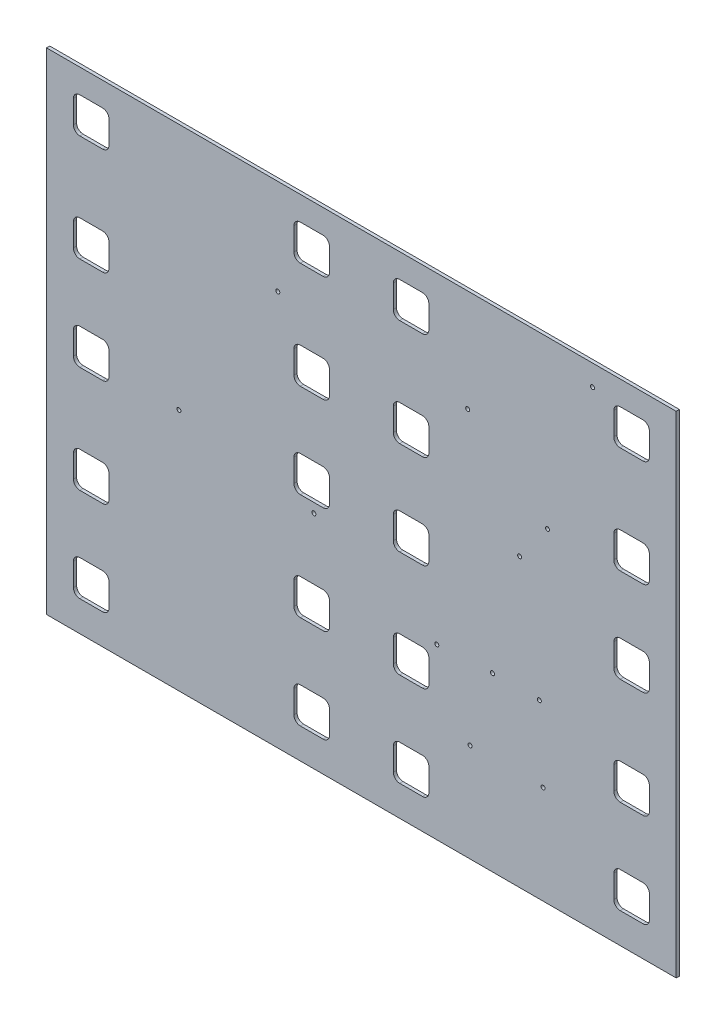
SolidWorks part; units mm, degrees
material "ABS"
ref_plane "X-Y Datum" through (0, 0, 0) normal (0, 0, 1) x (1, 0, 0)
ref_plane "X-Z Datum" through (0, 0, 0) normal (0, 1, 0) x (1, 0, 0)
ref_plane "Y-Z Datum" through (0, 0, 0) normal (1, 0, 0) x (0, 0, -1)
sketch "Sketch9" plane through (0, 0, 0) normal (0, 0, 1) x (1, 0, 0)
  line L0 (-82.7559, -182.5893) -> (-82.7583, -160.1613) construction
  line L1 (-89.109, -153.8119) -> (-111.537, -153.8143) construction
  line L2 (-117.8863, -160.165) -> (-117.8839, -182.593) construction
  line L3 (-111.5333, -188.9423) -> (-89.1053, -188.9399) construction
  line L4 (476.934, -311.4483) -> (476.8831, 172.8027)
  line L5 (476.8831, 172.8027) -> (-144.3755, 172.7375)
  line L6 (-144.3755, 172.7375) -> (-144.3246, -311.5135)
  line L7 (-144.3246, -311.5135) -> (476.934, -311.4483)
  line L8 (476.934, -311.4483) -> (476.8831, 172.8027)
  line L9 (476.8831, 172.8027) -> (-144.3755, 172.7375)
  line L10 (-144.3755, 172.7375) -> (-144.3246, -311.5135)
  line L11 (-144.3246, -311.5135) -> (476.934, -311.4483)
  line L12 (-111.5443, -83.8117) -> (-89.1163, -83.8093) construction
  line L13 (-82.767, -77.4587) -> (-82.7693, -55.0307) construction
  line L14 (-89.12, -48.6813) -> (-111.548, -48.6837) construction
  line L15 (-117.8973, -55.0344) -> (-117.895, -77.4624) construction
  line L16 (-82.7877, 120.2549) -> (-82.7901, 142.6829) construction
  line L17 (-89.1408, 149.0323) -> (-111.5688, 149.0299) construction
  line L18 (-117.9181, 142.6792) -> (-117.9157, 120.2512) construction
  line L19 (-111.5651, 113.9019) -> (-89.1371, 113.9043) construction
  line L20 (-111.554, 8.7713) -> (-89.126, 8.7737) construction
  line L21 (-117.9071, 37.5486) -> (-117.9047, 15.1206) construction
  line L22 (-89.1297, 43.9017) -> (-111.5577, 43.8993) construction
  line L23 (-82.7767, 15.1243) -> (-82.7791, 37.5523) construction
  line L24 (-82.7559, -182.5893) -> (-82.7583, -160.1613)
  line L25 (-89.109, -153.8119) -> (-111.537, -153.8143)
  line L26 (-117.8863, -160.165) -> (-117.8839, -182.593)
  line L27 (-111.5333, -188.9423) -> (-89.1053, -188.9399)
  line L28 (-111.5443, -83.8117) -> (-89.1163, -83.8093)
  line L29 (-82.767, -77.4587) -> (-82.7693, -55.0307)
  line L30 (-89.12, -48.6813) -> (-111.548, -48.6837)
  line L31 (-117.8973, -55.0344) -> (-117.895, -77.4624)
  line L32 (-82.7877, 120.2549) -> (-82.7901, 142.6829)
  line L33 (-89.1408, 149.0323) -> (-111.5688, 149.0299)
  line L34 (-117.9181, 142.6792) -> (-117.9157, 120.2512)
  line L35 (-111.5651, 113.9019) -> (-89.1371, 113.9043)
  line L36 (-111.554, 8.7713) -> (-89.126, 8.7737)
  line L37 (-117.9071, 37.5486) -> (-117.9047, 15.1206)
  line L38 (-89.1297, 43.9017) -> (-111.5577, 43.8993)
  line L39 (-82.7767, 15.1243) -> (-82.7791, 37.5523)
  line L40 (-82.7462, -275.1723) -> (-82.7486, -252.7443) construction
  line L41 (-89.0992, -246.3949) -> (-111.5272, -246.3973) construction
  line L42 (-117.8766, -252.748) -> (-117.8742, -275.176) construction
  line L43 (-111.5235, -281.5253) -> (-89.0955, -281.5229) construction
  line L44 (-82.7462, -275.1723) -> (-82.7486, -252.7443)
  line L45 (-89.0992, -246.3949) -> (-111.5272, -246.3973)
  line L46 (-117.8766, -252.748) -> (-117.8742, -275.176)
  line L47 (-111.5235, -281.5253) -> (-89.0955, -281.5229)
  arc A0 (-89.1053, -188.9399) -> (-82.7559, -182.5893) centre (-89.1059, -182.5899) ccw construction
  arc A1 (-82.7583, -160.1613) -> (-89.109, -153.8119) centre (-89.1083, -160.1619) ccw construction
  arc A2 (-111.537, -153.8143) -> (-117.8863, -160.165) centre (-111.5363, -160.1643) ccw construction
  arc A3 (-117.8839, -182.593) -> (-111.5333, -188.9423) centre (-111.5339, -182.5923) ccw construction
  arc A4 (-89.1163, -83.8093) -> (-82.767, -77.4587) centre (-89.117, -77.4593) ccw construction
  arc A5 (-82.7693, -55.0307) -> (-89.12, -48.6813) centre (-89.1193, -55.0313) ccw construction
  arc A6 (-111.548, -48.6837) -> (-117.8973, -55.0344) centre (-111.5473, -55.0337) ccw construction
  arc A7 (-117.895, -77.4624) -> (-111.5443, -83.8117) centre (-111.545, -77.4617) ccw construction
  arc A8 (-89.1371, 113.9043) -> (-82.7877, 120.2549) centre (-89.1377, 120.2543) ccw construction
  arc A9 (-82.7901, 142.6829) -> (-89.1408, 149.0323) centre (-89.1401, 142.6823) ccw construction
  arc A10 (-111.5688, 149.0299) -> (-117.9181, 142.6792) centre (-111.5681, 142.6799) ccw construction
  arc A11 (-117.9157, 120.2512) -> (-111.5651, 113.9019) centre (-111.5657, 120.2519) ccw construction
  arc A12 (-82.7791, 37.5523) -> (-89.1297, 43.9017) centre (-89.1291, 37.5517) ccw construction
  arc A13 (-89.126, 8.7737) -> (-82.7767, 15.1243) centre (-89.1267, 15.1237) ccw construction
  arc A14 (-117.9047, 15.1206) -> (-111.554, 8.7713) centre (-111.5547, 15.1213) ccw construction
  arc A15 (-111.5577, 43.8993) -> (-117.9071, 37.5486) centre (-111.5571, 37.5493) ccw construction
  arc A16 (-89.1053, -188.9399) -> (-82.7559, -182.5893) centre (-89.1059, -182.5899) ccw
  arc A17 (-82.7583, -160.1613) -> (-89.109, -153.8119) centre (-89.1083, -160.1619) ccw
  arc A18 (-111.537, -153.8143) -> (-117.8863, -160.165) centre (-111.5363, -160.1643) ccw
  arc A19 (-117.8839, -182.593) -> (-111.5333, -188.9423) centre (-111.5339, -182.5923) ccw
  arc A20 (-89.1163, -83.8093) -> (-82.767, -77.4587) centre (-89.117, -77.4593) ccw
  arc A21 (-82.7693, -55.0307) -> (-89.12, -48.6813) centre (-89.1193, -55.0313) ccw
  arc A22 (-111.548, -48.6837) -> (-117.8973, -55.0344) centre (-111.5473, -55.0337) ccw
  arc A23 (-117.895, -77.4624) -> (-111.5443, -83.8117) centre (-111.545, -77.4617) ccw
  arc A24 (-89.1371, 113.9043) -> (-82.7877, 120.2549) centre (-89.1377, 120.2543) ccw
  arc A25 (-82.7901, 142.6829) -> (-89.1408, 149.0323) centre (-89.1401, 142.6823) ccw
  arc A26 (-111.5688, 149.0299) -> (-117.9181, 142.6792) centre (-111.5681, 142.6799) ccw
  arc A27 (-117.9157, 120.2512) -> (-111.5651, 113.9019) centre (-111.5657, 120.2519) ccw
  arc A28 (-82.7791, 37.5523) -> (-89.1297, 43.9017) centre (-89.1291, 37.5517) ccw
  arc A29 (-89.126, 8.7737) -> (-82.7767, 15.1243) centre (-89.1267, 15.1237) ccw
  arc A30 (-117.9047, 15.1206) -> (-111.554, 8.7713) centre (-111.5547, 15.1213) ccw
  arc A31 (-111.5577, 43.8993) -> (-117.9071, 37.5486) centre (-111.5571, 37.5493) ccw
  arc A32 (-89.0955, -281.5229) -> (-82.7462, -275.1723) centre (-89.0962, -275.1729) ccw construction
  arc A33 (-111.5272, -246.3973) -> (-117.8766, -252.748) centre (-111.5266, -252.7473) ccw construction
  arc A34 (-117.8742, -275.176) -> (-111.5235, -281.5253) centre (-111.5242, -275.1753) ccw construction
  arc A35 (-89.0955, -281.5229) -> (-82.7462, -275.1723) centre (-89.0962, -275.1729) ccw
  arc A36 (-111.5272, -246.3973) -> (-117.8766, -252.748) centre (-111.5266, -252.7473) ccw
  arc A37 (-117.8742, -275.176) -> (-111.5235, -281.5253) centre (-111.5242, -275.1753) ccw
  arc A38 (-82.7486, -252.7443) -> (-89.0992, -246.3949) centre (-89.0986, -252.7449) ccw construction
  arc A39 (-82.7486, -252.7443) -> (-89.0992, -246.3949) centre (-89.0986, -252.7449) ccw
  dimension "D1" = 0
extrude "Boss-Extrude2" add sketch "Sketch9" along normal blind 3.175 contours L10 L11 L8 L9 A39 L44 A35 L47 A37 L46 A36 L45 A31 L38 A28 L39 A29 L36 A30 L37 A27 L34 A26 L33 A25 L32 A24 L35 A23 L31 A22 L30 A21 L29 A20 L28 A19 L26 A18 L25 A17 L24 A16 L27 | L44 A39 L45 A36 L46 A37 L47 A35 | L26 A19 L27 A16 L24 A17 L25 A18 | L38 A31 L37 A30 L36 A29 L39 A28 | L34 A27 L35 A24 L32 A25 L33 A26 | L31 A23 L28 A20 L29 A21 L30 A22 region at (171.7018, -69.3676, 0) region at (-100.3211, -171.3771, 0) region at (-100.3322, -66.2465, 0) region at (-100.3529, 131.4671, 0) region at (-100.3419, 26.3365, 0) region at (-100.3114, -263.9601, 0)
sketch "Sketch10" plane through (0, 0, 3.175) normal (0, 0, 1) x (1, 0, 0)
  line L4 (476.934, -311.4483) -> (476.8831, 172.8027)
  line L5 (476.8831, 172.8027) -> (-144.3755, 172.7375)
  line L6 (-144.3755, 172.7375) -> (-144.3246, -311.5135)
  line L7 (-144.3246, -311.5135) -> (476.934, -311.4483)
  line L8 (476.934, -311.4483) -> (476.8831, 172.8027)
  line L9 (476.8831, 172.8027) -> (-144.3755, 172.7375)
  line L10 (-144.3755, 172.7375) -> (-144.3246, -311.5135)
  line L11 (-144.3246, -311.5135) -> (476.934, -311.4483)
  line L12 (-117.8863, -160.165) -> (-117.8839, -182.593)
  line L13 (-111.5333, -188.9423) -> (-89.1053, -188.9399)
  line L14 (-82.7559, -182.5893) -> (-82.7583, -160.1613)
  line L15 (-89.109, -153.8119) -> (-111.537, -153.8143)
  line L16 (-117.8863, -160.165) -> (-117.8839, -182.593)
  line L17 (-111.5333, -188.9423) -> (-89.1053, -188.9399)
  line L18 (-82.7559, -182.5893) -> (-82.7583, -160.1613)
  line L19 (-89.109, -153.8119) -> (-111.537, -153.8143)
  line L20 (-117.8766, -252.748) -> (-117.8742, -275.176)
  line L21 (-89.0992, -246.3949) -> (-111.5272, -246.3973)
  line L22 (-82.7462, -275.1723) -> (-82.7486, -252.7443)
  line L23 (-111.5235, -281.5253) -> (-89.0955, -281.5229)
  line L24 (-117.8766, -252.748) -> (-117.8742, -275.176)
  line L25 (-89.0992, -246.3949) -> (-111.5272, -246.3973)
  line L26 (-82.7462, -275.1723) -> (-82.7486, -252.7443)
  line L27 (-111.5235, -281.5253) -> (-89.0955, -281.5229)
  line L28 (-89.12, -48.6813) -> (-111.548, -48.6837)
  line L29 (-117.8973, -55.0344) -> (-117.895, -77.4624)
  line L30 (-111.5443, -83.8117) -> (-89.1163, -83.8093)
  line L31 (-82.767, -77.4587) -> (-82.7693, -55.0307)
  line L32 (-89.12, -48.6813) -> (-111.548, -48.6837)
  line L33 (-117.8973, -55.0344) -> (-117.895, -77.4624)
  line L34 (-111.5443, -83.8117) -> (-89.1163, -83.8093)
  line L35 (-82.767, -77.4587) -> (-82.7693, -55.0307)
  line L36 (-82.7877, 120.2549) -> (-82.7901, 142.6829)
  line L37 (-111.5651, 113.9019) -> (-89.1371, 113.9043)
  line L38 (-117.9181, 142.6792) -> (-117.9157, 120.2512)
  line L39 (-89.1408, 149.0323) -> (-111.5688, 149.0299)
  line L40 (-82.7877, 120.2549) -> (-82.7901, 142.6829)
  line L41 (-111.5651, 113.9019) -> (-89.1371, 113.9043)
  line L42 (-117.9181, 142.6792) -> (-117.9157, 120.2512)
  line L43 (-89.1408, 149.0323) -> (-111.5688, 149.0299)
  line L44 (-111.554, 8.7713) -> (-89.126, 8.7737)
  line L45 (-82.7767, 15.1243) -> (-82.7791, 37.5523)
  line L46 (-89.1297, 43.9017) -> (-111.5577, 43.8993)
  line L47 (-117.9071, 37.5486) -> (-117.9047, 15.1206)
  line L48 (-111.554, 8.7713) -> (-89.126, 8.7737)
  line L49 (-82.7767, 15.1243) -> (-82.7791, 37.5523)
  line L50 (-89.1297, 43.9017) -> (-111.5577, 43.8993)
  line L51 (-117.9071, 37.5486) -> (-117.9047, 15.1206)
  arc A4 (-117.8839, -182.593) -> (-111.5333, -188.9423) centre (-111.5339, -182.5923) ccw
  arc A5 (-89.1053, -188.9399) -> (-82.7559, -182.5893) centre (-89.1059, -182.5899) ccw
  arc A6 (-82.7583, -160.1613) -> (-89.109, -153.8119) centre (-89.1083, -160.1619) ccw
  arc A7 (-111.537, -153.8143) -> (-117.8863, -160.165) centre (-111.5363, -160.1643) ccw
  arc A8 (-117.8839, -182.593) -> (-111.5333, -188.9423) centre (-111.5339, -182.5923) ccw
  arc A9 (-89.1053, -188.9399) -> (-82.7559, -182.5893) centre (-89.1059, -182.5899) ccw
  arc A10 (-82.7583, -160.1613) -> (-89.109, -153.8119) centre (-89.1083, -160.1619) ccw
  arc A11 (-111.537, -153.8143) -> (-117.8863, -160.165) centre (-111.5363, -160.1643) ccw
  arc A12 (-111.5272, -246.3973) -> (-117.8766, -252.748) centre (-111.5266, -252.7473) ccw
  arc A13 (-82.7486, -252.7443) -> (-89.0992, -246.3949) centre (-89.0986, -252.7449) ccw
  arc A14 (-89.0955, -281.5229) -> (-82.7462, -275.1723) centre (-89.0962, -275.1729) ccw
  arc A15 (-117.8742, -275.176) -> (-111.5235, -281.5253) centre (-111.5242, -275.1753) ccw
  arc A16 (-111.5272, -246.3973) -> (-117.8766, -252.748) centre (-111.5266, -252.7473) ccw
  arc A17 (-82.7486, -252.7443) -> (-89.0992, -246.3949) centre (-89.0986, -252.7449) ccw
  arc A18 (-89.0955, -281.5229) -> (-82.7462, -275.1723) centre (-89.0962, -275.1729) ccw
  arc A19 (-117.8742, -275.176) -> (-111.5235, -281.5253) centre (-111.5242, -275.1753) ccw
  arc A20 (-111.548, -48.6837) -> (-117.8973, -55.0344) centre (-111.5473, -55.0337) ccw
  arc A21 (-117.895, -77.4624) -> (-111.5443, -83.8117) centre (-111.545, -77.4617) ccw
  arc A22 (-89.1163, -83.8093) -> (-82.767, -77.4587) centre (-89.117, -77.4593) ccw
  arc A23 (-82.7693, -55.0307) -> (-89.12, -48.6813) centre (-89.1193, -55.0313) ccw
  arc A24 (-111.548, -48.6837) -> (-117.8973, -55.0344) centre (-111.5473, -55.0337) ccw
  arc A25 (-117.895, -77.4624) -> (-111.5443, -83.8117) centre (-111.545, -77.4617) ccw
  arc A26 (-89.1163, -83.8093) -> (-82.767, -77.4587) centre (-89.117, -77.4593) ccw
  arc A27 (-82.7693, -55.0307) -> (-89.12, -48.6813) centre (-89.1193, -55.0313) ccw
  arc A28 (-89.1371, 113.9043) -> (-82.7877, 120.2549) centre (-89.1377, 120.2543) ccw
  arc A29 (-117.9157, 120.2512) -> (-111.5651, 113.9019) centre (-111.5657, 120.2519) ccw
  arc A30 (-111.5688, 149.0299) -> (-117.9181, 142.6792) centre (-111.5681, 142.6799) ccw
  arc A31 (-82.7901, 142.6829) -> (-89.1408, 149.0323) centre (-89.1401, 142.6823) ccw
  arc A32 (-89.1371, 113.9043) -> (-82.7877, 120.2549) centre (-89.1377, 120.2543) ccw
  arc A33 (-117.9157, 120.2512) -> (-111.5651, 113.9019) centre (-111.5657, 120.2519) ccw
  arc A34 (-111.5688, 149.0299) -> (-117.9181, 142.6792) centre (-111.5681, 142.6799) ccw
  arc A35 (-82.7901, 142.6829) -> (-89.1408, 149.0323) centre (-89.1401, 142.6823) ccw
  arc A36 (-89.126, 8.7737) -> (-82.7767, 15.1243) centre (-89.1267, 15.1237) ccw
  arc A37 (-82.7791, 37.5523) -> (-89.1297, 43.9017) centre (-89.1291, 37.5517) ccw
  arc A38 (-111.5577, 43.8993) -> (-117.9071, 37.5486) centre (-111.5571, 37.5493) ccw
  arc A39 (-117.9047, 15.1206) -> (-111.554, 8.7713) centre (-111.5547, 15.1213) ccw
  arc A40 (-89.126, 8.7737) -> (-82.7767, 15.1243) centre (-89.1267, 15.1237) ccw
  arc A41 (-82.7791, 37.5523) -> (-89.1297, 43.9017) centre (-89.1291, 37.5517) ccw
  arc A42 (-111.5577, 43.8993) -> (-117.9071, 37.5486) centre (-111.5571, 37.5493) ccw
  arc A43 (-117.9047, 15.1206) -> (-111.554, 8.7713) centre (-111.5547, 15.1213) ccw
  dimension "D1" = 0
  dimension "D2" = 0
  dimension "D3" = 0
  dimension "D4" = 0
  dimension "D5" = 0
  dimension "D6" = 0
extrude "Cut-Extrude6" cut sketch "Sketch10" against normal through all contours L40 A35 L43 A34 L42 A33 L41 A32 | L51 A43 L48 A40 L49 A41 L50 A42 | L35 A27 L32 A24 L33 A25 L34 A26 | L19 A11 L16 A8 L17 A9 L18 A10 | L24 A19 L27 A18 L26 A17 L25 A16 region at (-100.3211, -171.3771, 3.175) region at (-100.3114, -263.9601, 3.175) region at (-100.3322, -66.2465, 3.175) region at (-100.3529, 131.4671, 3.175) region at (-100.3419, 26.3365, 3.175)
pattern_linear "LPattern2" count 2 spacing 217.5764 along (1, 0.0001, 0) of "Cut-Extrude6"
ref_plane "Plane1" through (166.272, 0.0175, 0) normal (-1, -0.0001, 0) x (0, 0, 1)
mirror "Mirror1" about plane through (166.272, 0.0175, 0) normal (-1, -0.0001, 0) of "LPattern2", "Cut-Extrude6"
sketch "Sketch11" plane through (0, 0, 3.175) normal (0, 0, 1) x (1, 0, 0)
  circle A3 centre (295.6537, -141.6048) radius 1.9939
  circle A5 centre (295.6537, -141.6048) radius 1.9939
  circle A7 centre (394.3353, 152.1565) radius 1.9939
  circle A9 centre (394.3353, 152.1565) radius 1.9939
  circle A11 centre (271.1937, 71.8561) radius 1.9939
  circle A13 centre (271.1937, 71.8561) radius 1.9939
  circle A15 centre (83.7969, 78.6239) radius 1.9939
  circle A17 centre (83.7969, 78.6239) radius 1.9939
  circle A19 centre (-13.7373, -71.3863) radius 1.9939
  circle A21 centre (-13.7373, -71.3863) radius 1.9939
  circle A23 centre (349.9239, 8.7889) radius 1.9939
  circle A44 centre (349.9239, 8.7889) radius 1.9939
  circle A45 centre (322.4278, -28.338) radius 1.9939
  circle A46 centre (322.4278, -28.338) radius 1.9939
  circle A47 centre (341.8537, -141.6) radius 1.9939
  circle A48 centre (341.8537, -141.6) radius 1.9939
  circle A49 centre (345.5113, -214.3496) radius 1.9939
  circle A50 centre (345.5113, -214.3496) radius 1.9939
  circle A51 centre (119.4061, -93.0712) radius 1.9939
  circle A52 centre (119.4061, -93.0712) radius 1.9939
  circle A53 centre (240.6965, -144.4935) radius 1.9939
  circle A54 centre (240.6965, -144.4935) radius 1.9939
  circle A55 centre (273.5113, -214.3572) radius 1.9939
  circle A56 centre (273.5113, -214.3572) radius 1.9939
  dimension "D1" = 0
  dimension "D2" = 0
  dimension "D3" = 0
  dimension "D4" = 0
  dimension "D5" = 0
  dimension "D6" = 0
  dimension "D7" = 0
  dimension "D8" = 0
  dimension "D9" = 0
  dimension "D10" = 0
  dimension "D11" = 0
  dimension "D12" = 0
extrude "Cut-Extrude7" cut sketch "Sketch11" against normal through all
